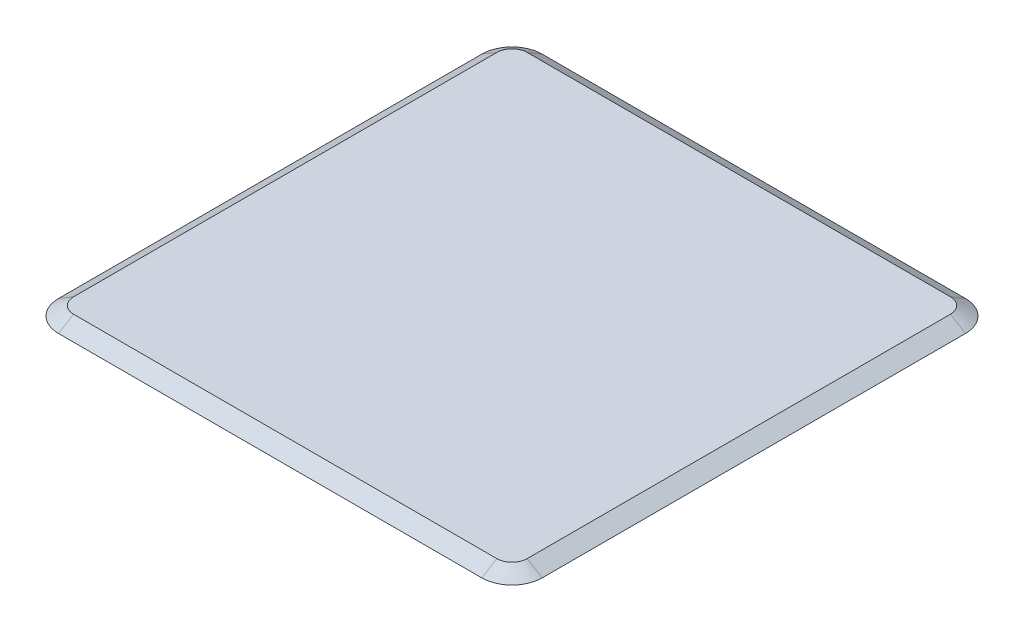
SolidWorks part; units mm, degrees
ref_plane "Front Plane" through (0, 0, 0) normal (0, 0, 1) x (1, 0, 0)
ref_plane "Top Plane" through (0, 0, 0) normal (0, 1, 0) x (1, 0, 0)
ref_plane "Right Plane" through (0, 0, 0) normal (1, 0, 0) x (0, 0, -1)
sketch "Sketch1" plane through (0, 0, 0) normal (0, 1, 0) x (1, 0, 0)
  line L1 (-35, 40) -> (35, 40)
  line L2 (-40, 35) -> (-40, -35)
  line L3 (-35, -40) -> (35, -40)
  line L4 (40, 35) -> (40, -35)
  arc A0 (35, -40) -> (40, -35) centre (35, -35) ccw
  arc A1 (40, 35) -> (35, 40) centre (35, 35) ccw
  arc A2 (-35, -40) -> (-40, -35) centre (-35, -35) cw
  arc A3 (-40, 35) -> (-35, 40) centre (-35, 35) cw
  point P7 (40, -40)
  point P10 (40, 40)
  point P15 (-40, 40)
  dimension "D5" = 5
  dimension "D1" = 80
  dimension "D2" = 80
  dimension "D3" = 40
  dimension "D4" = 40
extrude "Boss-Extrude1" add sketch "Sketch1" along normal blind 1.5
chamfer "Chamfer1" distance 1.5 distance2 2.5 8 edges at (-38.5355, 1.5, 38.5355) (-40, 1.5, 0) (-38.5355, 1.5, -38.5355) (0, 1.5, -40) (38.5355, 1.5, -38.5355) (0, 1.5, 40) (38.5355, 1.5, 38.5355) (40, 1.5, 0) first distance on face at (-38.0178, 0.75, 38.0178) first distance on face at (-40, 0.75, 0) first distance on face at (-38.0178, 0.75, -38.0178) first distance on face at (0, 0.75, -40) first distance on face at (38.0178, 0.75, -38.0178) first distance on face at (0, 0.75, 40) first distance on face at (38.0178, 0.75, 38.0178) first distance on face at (40, 0.75, 0)
